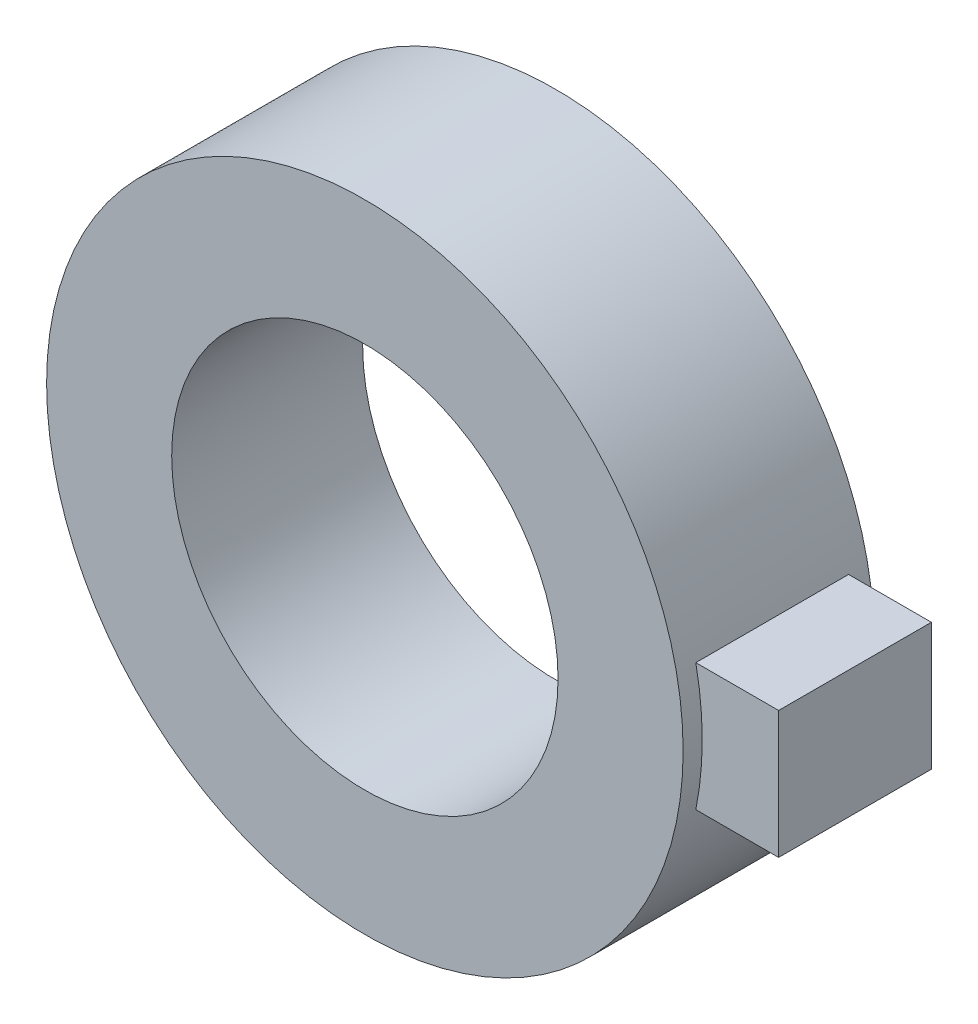
SolidWorks part; units mm, degrees
material "AISI Type 316L stainless steel"
ref_plane "Front Plane" through (0, 0, 0) normal (0, 0, 1) x (1, 0, 0)
ref_plane "Top Plane" through (0, 0, 0) normal (0, 1, 0) x (1, 0, 0)
ref_plane "Right Plane" through (0, 0, 0) normal (1, 0, 0) x (0, 0, -1)
sketch "Extrude sketch 1" plane through (0, 0, 0) normal (0, 0, 1) x (1, 0, 0)
  circle A0 centre (0, 0) radius 50
  circle A1 centre (0, 0) radius 30.35
  dimension "D1" = 60.7
  dimension "D2" = 100
extrude "Extrude 1" add sketch "Extrude sketch 1" along normal blind 30 separate body
sketch "Extrude sketch 2" plane through (0, 0, 0) normal (0, 0, 1) x (1, 0, 0)
  line L0 (62, -10) -> (62, 10)
  line L1 (62, 10) -> (46, 10)
  line L2 (46, 10) -> (46, -10)
  line L3 (46, -10) -> (62, -10)
  dimension "D1" = 16
  dimension "D2" = 20
extrude "Extrude 2" add sketch "Extrude sketch 2" along normal blind 24 from offset 3 separate body
combine bodies "Combine (weld / assembly of features)" operation type add bodies to combine 102 101
